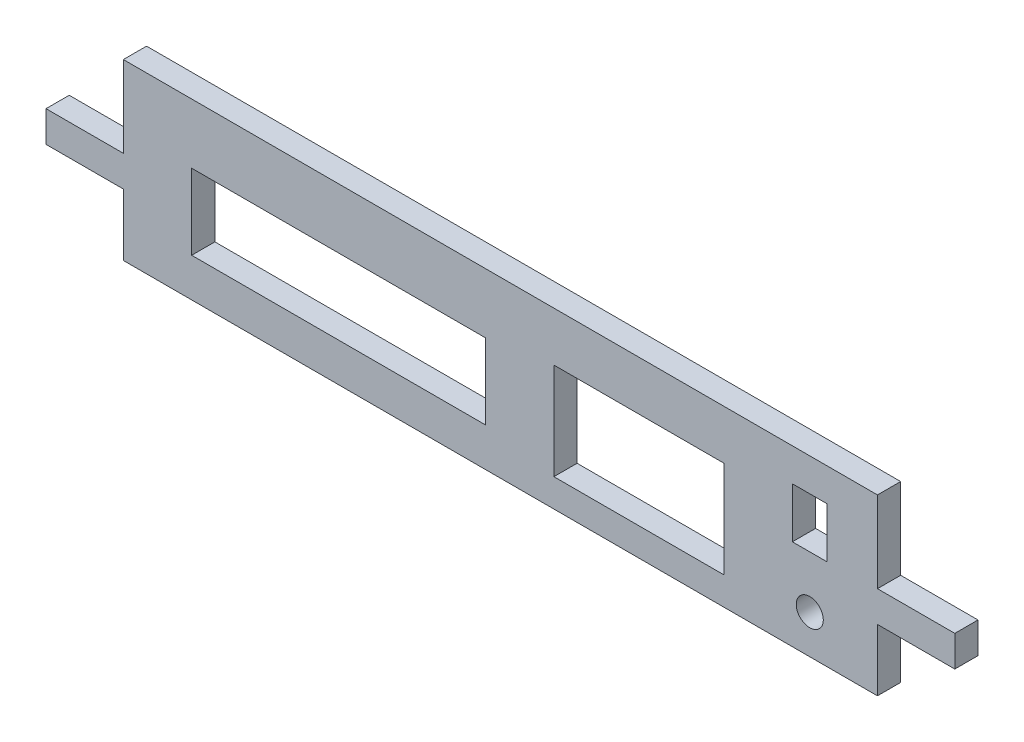
SolidWorks part; units mm, degrees
material "Balsa"
ref_plane "Plano frontal" through (0, 0, 0) normal (0, 0, 1) x (1, 0, 0)
ref_plane "Plano superior" through (0, 0, 0) normal (0, 1, 0) x (1, 0, 0)
ref_plane "Plano direito" through (0, 0, 0) normal (1, 0, 0) x (0, 0, -1)
sketch "Esboço1" plane through (0, 0, 0) normal (0, 0, 1) x (1, 0, 0)
  line L0 (-97.5, -6.5) -> (-97.5, -22.5)
  line L1 (-97.5, -6.5) -> (-117.5, -6.5)
  line L2 (-97.5, 22.5) -> (-97.5, 1.5)
  line L3 (-97.5, -22.5) -> (97.5, -22.5)
  line L4 (97.5, 22.5) -> (97.5, 1.5)
  line L5 (97.5, 1.5) -> (117.5, 1.5)
  line L6 (-97.5, -22.5) -> (97.5, 22.5) construction
  line L7 (-97.5, 1.5) -> (-117.5, 1.5)
  line L8 (-117.5, -6.5) -> (-117.5, 1.5)
  line L9 (97.5, -6.5) -> (117.5, -6.5)
  line L10 (117.5, -6.5) -> (117.5, 1.5)
  line L11 (97.5, -6.5) -> (97.5, -22.5)
  line L12 (0, 0) -> (0, 44.2972) construction
  line L13 (-97.5, -8.503) -> (-79.8333, -8.503) construction
  line L14 (-3.8333, -8.503) -> (13.8333, -8.503) construction
  line L15 (57.8333, 4.4718) -> (75.5, 4.4718) construction
  line L20 (-97.5, 22.5) -> (97.5, 22.5)
  line L47 (-97.5, 22.5) -> (97.5, -22.5) construction
  line L48 (-79.8333, -12.5) -> (-3.8333, -12.5)
  line L49 (-79.8333, -12.5) -> (-79.8333, 7)
  line L50 (-79.8333, 7) -> (-3.8333, 7)
  line L51 (-3.8333, -12.5) -> (-3.8333, 7)
  line L52 (-79.8333, -12.5) -> (-3.8333, 7) construction
  line L53 (-79.8333, 7) -> (-3.8333, -12.5) construction
  line L54 (13.8333, 9.75) -> (57.8333, 9.75)
  line L55 (13.8333, 9.75) -> (13.8333, -15.25)
  line L56 (13.8333, -15.25) -> (57.8333, -15.25)
  line L57 (57.8333, 9.75) -> (57.8333, -15.25)
  line L58 (13.8333, 9.75) -> (57.8333, -15.25) construction
  line L59 (13.8333, -15.25) -> (57.8333, 9.75) construction
  line L60 (75.5, 14) -> (84.5, 14)
  line L61 (75.5, 14) -> (75.5, 1)
  line L62 (75.5, 1) -> (84.5, 1)
  line L63 (84.5, 14) -> (84.5, 1)
  line L64 (75.5, 14) -> (84.5, 1) construction
  line L65 (75.5, 1) -> (84.5, 14) construction
  circle A0 centre (80, -12.5) radius 3.5
  point P0 (0, 0)
  point P16 (0, 0)
  point P23 (-79.5, -8.503)
  point P25 (80, 7.5)
  point P37 (35.8333, -2.75)
  point P54 (-41.8333, -2.75)
  dimension "D22" = 7
  dimension "D3" = 195
  dimension "D4" = 45
  dimension "D5" = 20
  dimension "D6" = 8
  dimension "D7" = 16
  dimension "D13" = 19.5
  dimension "D14" = 76
  dimension "D16" = 10
  dimension "D17" = 44
  dimension "D18" = 25
  dimension "D20" = 13
  dimension "D21" = 9
  dimension "D23" = 13
  dimension "D24" = 10
  dimension "D25" = 20
extrude "Ressalto-extrusão1" add sketch "Esboço1" along normal blind 6 contours L20 L8 L2 L3 L4 A0 L51 L48 L49 L50 region at (1.5952, 0.9287, 0)
